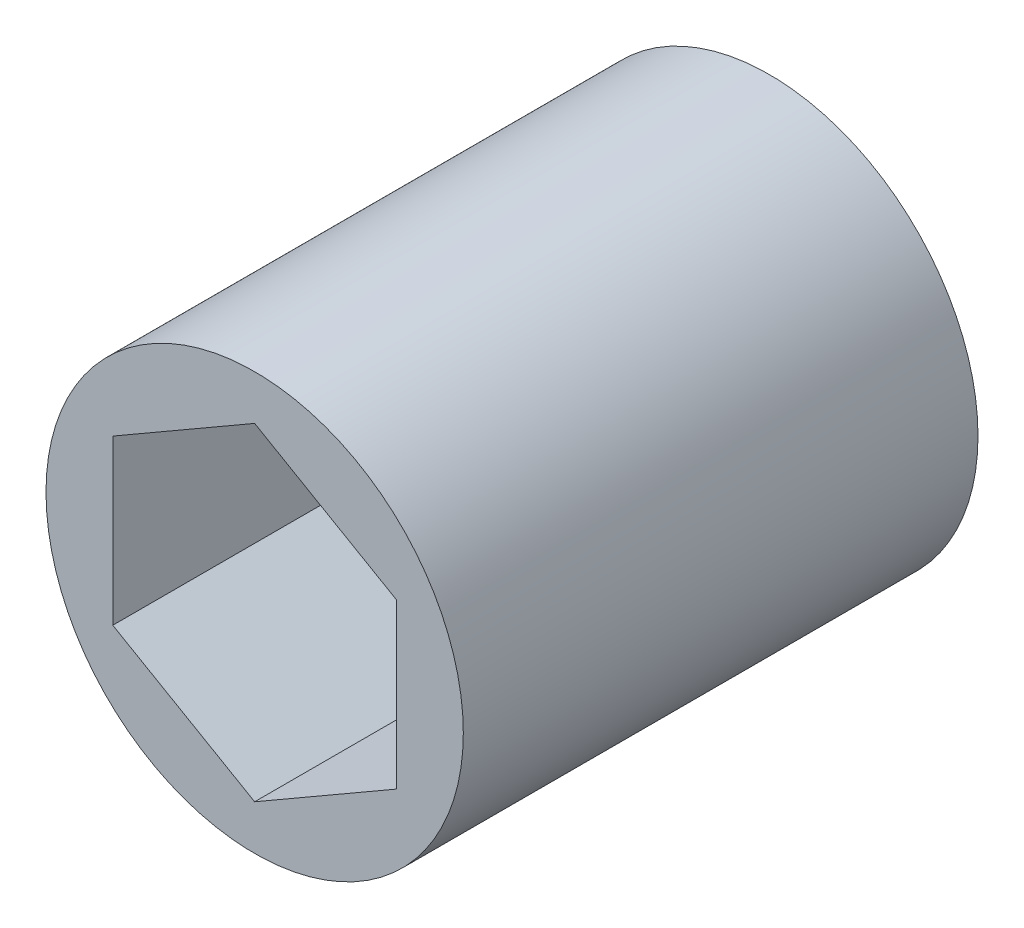
SolidWorks part; units mm, degrees
material "PET"
ref_plane "Front Plane" through (0, 0, 0) normal (0, 0, 1) x (1, 0, 0)
ref_plane "Top Plane" through (0, 0, 0) normal (0, 1, 0) x (1, 0, 0)
ref_plane "Right Plane" through (0, 0, 0) normal (1, 0, 0) x (0, 0, -1)
sketch "Sketch1" plane through (0, 0, 0) normal (0, 0, 1) x (1, 0, 0)
  line L1 (0, 7.479) -> (-6.477, 3.7395)
  line L2 (-6.477, 3.7395) -> (-6.477, -3.7395)
  line L3 (-6.477, -3.7395) -> (0, -7.479)
  line L4 (0, -7.479) -> (6.477, -3.7395)
  line L5 (6.477, -3.7395) -> (6.477, 3.7395)
  line L6 (6.477, 3.7395) -> (0, 7.479)
  circle A0 centre (0, 0) radius 9.525
  circle A1 centre (0, 0) radius 6.477 construction
  dimension "D1" = 19.05
  dimension "D2" = 12.954
extrude "Boss-Extrude1" add sketch "Sketch1" along normal mid plane 23.495
